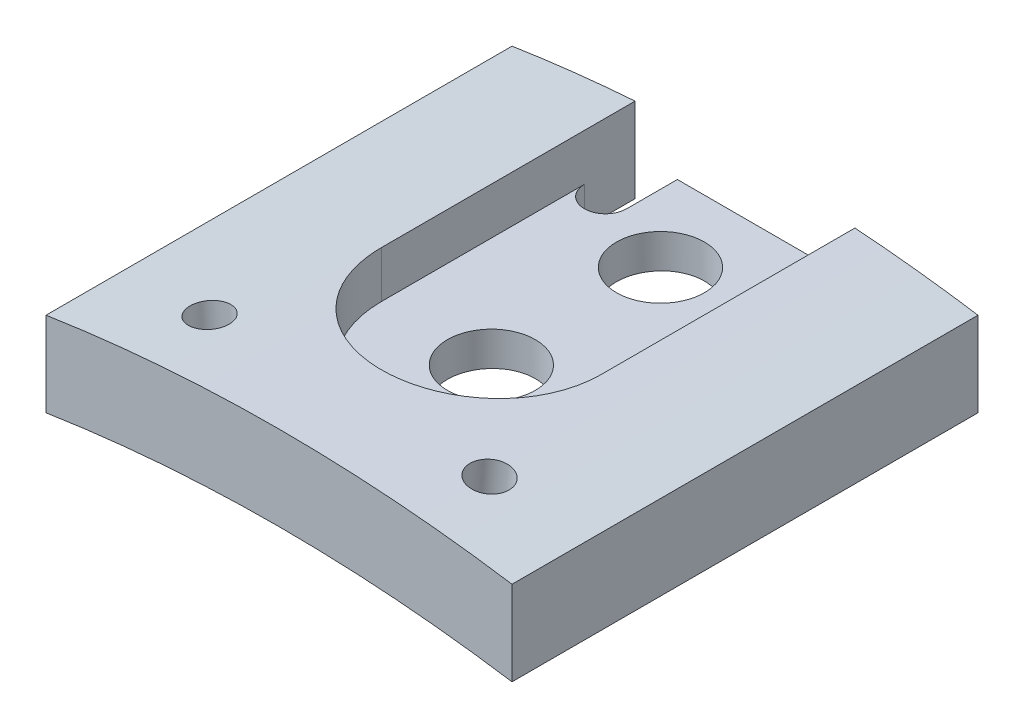
SolidWorks part; units mm, degrees
ref_plane "Front Plane" through (0, 0, 0) normal (0, 0, 1) x (1, 0, 0)
ref_plane "Top Plane" through (0, 0, 0) normal (0, 1, 0) x (1, 0, 0)
ref_plane "Right Plane" through (0, 0, 0) normal (1, 0, 0) x (0, 0, -1)
sketch "Sketch1" plane through (0, 0, 0) normal (0, 0, 1) x (1, 0, 0)
  line L1 (0, 0) -> (-35, 0)
  line L2 (0, 0) -> (0, -12.7)
  line L3 (0, -12.7) -> (-35, -12.7)
  line L4 (-35, 0) -> (-35, -12.7)
  arc A0 (-35, -12.7) -> (0, -12.7) centre (-17.5, -125.7809) cw
  dimension "D1" = 35
  dimension "D3" = 114.427
  dimension "D2" = 12.7
extrude "Boss-Extrude1" add sketch "Sketch1" along normal blind 35 contours L4 A0 L2 L1 region at (-17.5, -5.9076, 0)
ref_plane "Plane2" through (0, -11.3539, 0) normal (0, -1, 0) x (1, 0, 0)
ref_plane "Plane3" through (-1.0808, -12.3533, 0) normal (-0.0872, -0.9962, 0) x (0.9962, -0.0872, 0)
ref_plane "Plane4" through (0.8149, -9.3145, 0) normal (0.0872, -0.9962, 0) x (0.9962, 0.0872, 0)
sketch "Sketch3" plane through (0, 0, 35) normal (0, 0, 1) x (1, 0, 0)
  line L0 (-17.5, -125.6524) -> (-17.5, 0) construction
  line L1 (0, 0) -> (-35, 0) construction
  line L2 (-17.5, -125.6524) -> (-6.5068, 0) construction
  line L3 (-17.5, -125.6524) -> (-28.4932, 0) construction
  circle A0 centre (-17.5, -125.6524) radius 114.3
  dimension "D1" = 228.6
  dimension "D2" = 5
  dimension "D3" = 5
sketch "Sketch6" plane through (-1.0808, -12.3533, 0) normal (-0.0872, -0.9962, 0) x (0.9962, -0.0872, 0)
  line L0 (-6.4821, 35) -> (-6.4821, 0) construction
  line L1 (107.8179, 35) -> (-120.7821, 35) construction
  line L2 (1.1069, 0) -> (-33.7599, 0) construction
  circle A0 centre (-6.4821, 29.7028) radius 1.4732
  dimension "D1" = 2.9464
  dimension "D2" = 29.7028
extrude "Cut-Extrude4" cut sketch "Sketch6" against normal through all and the other way through all
sketch "Sketch7" plane through (0.8149, -9.3145, 0) normal (0.0872, -0.9962, 0) x (0.9962, 0.0872, 0)
  line L0 (-28.3847, 35) -> (-28.3847, 0) construction
  line L1 (85.9153, 35) -> (-142.6847, 35) construction
  line L2 (-1.1069, 0) -> (-35.9737, 0) construction
  circle A0 centre (-28.3847, 29.7028) radius 1.4732
  dimension "D1" = 2.9464
  dimension "D2" = 29.7028
extrude "Cut-Extrude5" cut sketch "Sketch7" against normal through all and the other way through all
sketch "Sketch8" plane through (0, 0, 0) normal (0, 0, -1) x (-1, 0, 0)
  line L0 (0, -6.35) -> (35, -6.35) construction
  line L3 (35, -12.7) -> (35, 0)
  line L4 (35, 0) -> (0, 0)
  line L5 (0, 0) -> (0, -12.7)
  line L6 (35, -12.7) -> (35, 0)
  line L7 (35, 0) -> (0, 0)
  line L8 (0, 0) -> (0, -12.7)
  arc A0 (0, -6.35) -> (35, -6.35) centre (17.5, -119.4309) cw
  arc A1 (35, -12.7) -> (0, -12.7) centre (17.5, -125.7809) ccw
  arc A2 (35, -12.7) -> (0, -12.7) centre (17.5, -125.7809) ccw
  line M6 (35, 0) -> (0, 0)
  line M7 (0, 0) -> (0, -12.7)
  dimension "D3" = 114.427
  dimension "D2" = 6.35
  dimension "D1" = 0
extrude "Cut-Extrude6" cut sketch "Sketch8" against normal through all contours A0 L6 M7 M6 region at (-17.5, -2.7405, 0)
sketch "Sketch9" plane through (0, 0, 0) normal (0, 0, -1) x (-1, 0, 0)
  line L0 (17.5, -11.3539) -> (17.5, -5.0039) construction
  line L2 (35, -12.7) -> (35, -6.35)
  line L3 (0, -6.35) -> (0, -12.7)
  line L4 (35, -12.7) -> (35, -6.35)
  line L5 (0, -6.35) -> (0, -12.7)
  arc A2 (35, -6.35) -> (0, -6.35) centre (17.5, -119.4309) ccw
  arc A3 (35, -12.7) -> (0, -12.7) centre (17.5, -125.7809) ccw
  arc A4 (35, -6.35) -> (0, -6.35) centre (17.5, -119.4309) ccw
  arc A5 (35, -12.7) -> (0, -12.7) centre (17.5, -125.7809) ccw
  dimension "D1" = 0
ref_plane "Plane5" through (-17.5, -5.0039, 0) normal (0, 1, 0) x (-1, 0, 0)
sketch "Sketch10" plane through (-17.5, -5.0039, 0) normal (0, 1, 0) x (-1, 0, 0)
  line L0 (-17.5, 27.5) -> (17.5, 27.5) construction
  line L1 (-17.5, 35) -> (-17.5, 0) construction
  line L2 (17.5, 35) -> (17.5, 0) construction
  line L3 (-17.5, 0) -> (17.5, 0) construction
  line L4 (0, 27.5) -> (0, 0) construction
  line L5 (-6.985, 19.05) -> (-6.985, 6.35)
  line L6 (6.985, 19.05) -> (6.985, 6.35)
  line L7 (-8.255, 19.05) -> (-8.255, 6.35)
  line L8 (8.255, 19.05) -> (8.255, 6.35)
  line L9 (-8.255, 6.35) -> (-8.255, 0)
  line L10 (-17.5, 0) -> (17.5, 0) construction
  line L11 (-8.255, 0) -> (8.255, 0)
  line L12 (8.255, 0) -> (8.255, 6.35)
  line L14 (-8.255, 0) -> (8.255, 0)
  line L15 (-8.255, 0) -> (-8.255, -2.465)
  line L16 (-8.255, -2.465) -> (8.255, -2.465)
  line L17 (8.255, 0) -> (8.255, -2.465)
  circle A0 centre (0, 19.05) radius 3.302
  circle A1 centre (0, 6.35) radius 3.302
  arc A2 (6.985, 19.05) -> (-6.985, 19.05) centre (0, 19.05) ccw
  arc A3 (-6.985, 6.35) -> (6.985, 6.35) centre (0, 6.35) ccw
  arc A4 (8.255, 19.05) -> (-8.255, 19.05) centre (0, 19.05) ccw
  arc A5 (-8.255, 6.35) -> (8.255, 6.35) centre (0, 6.35) ccw
  dimension "D4" = 6.604
  dimension "D5" = 6.604
  dimension "D6" = 13.97
  dimension "D7" = 13.97
  dimension "D1" = 27.5
  dimension "D2" = 6.35
  dimension "D3" = 12.7
  dimension "D8" = 1.27
extrude "Cut-Extrude7" cut sketch "Sketch10" against normal through all contours A0 | A1 region at (-17.5, -5.0039, 19.05) region at (-17.5, -5.0039, 6.35)
extrude "Cut-Extrude8" cut sketch "Sketch10<3>" against normal blind 3.81 contours L7 A5 L8 A4 A3 L5 A2 L6 | L5 A3 L6 A2 A0 A1 | A5 L9 L11 | A5 L11 L15 L16 L17 L14 | A5 L14 L12 | L14 A5 L11 A3 | L14 A3 region at (-17.5, -5.0039, 12.8241) region at (-10.1959, -5.0039, 12.7) region at (-17.5, -5.0039, -0.8839) region at (-17.5, -5.0039, -0.255) region at (-17.5, -5.0039, -2.0719) region at (-10.1025, -5.0039, 1.5245) region at (-24.8975, -5.0039, 1.5245)
sketch "Sketch10<3>" plane through (-17.5, -5.0039, 0) normal (0, 1, 0) x (-1, 0, 0) same geometry as "Sketch10"
sketch "Sketch11" plane through (0, -8.8139, 0) normal (0, 1, 0) x (1, 0, 0)
  line L0 (-22.58, 0) -> (-22.58, -3.81)
  line L1 (-22.58, -3.81) -> (-25.755, -3.81) construction
  line L3 (-9.245, 0) -> (-25.755, 0)
  line L4 (-25.755, 0) -> (-25.755, -19.05)
  line L5 (-9.245, -19.05) -> (-9.245, 0)
  line L6 (-9.245, 0) -> (-25.755, 0)
  line L7 (-25.755, 0) -> (-25.755, -19.05)
  line L8 (-9.245, -19.05) -> (-9.245, 0)
  arc A0 (-25.755, -3.81) -> (-22.58, -3.81) centre (-24.1675, -3.81) ccw
  arc A1 (-25.755, -19.05) -> (-9.245, -19.05) centre (-17.5, -19.05) ccw
  arc A2 (-25.755, -19.05) -> (-9.245, -19.05) centre (-17.5, -19.05) ccw
  line M7 (-9.245, 0) -> (-25.755, 0)
  line M8 (-25.755, 0) -> (-25.755, -19.05)
  dimension "D2" = 3.175
  dimension "D3" = 3.81
  dimension "D1" = 0
extrude "Cut-Extrude9" cut sketch "Sketch11" against normal through all contours L1 L0 M7 M8 | A0 L1 region at (-24.1675, -8.8139, 1.905) region at (-24.1675, -8.8139, 4.4838)
